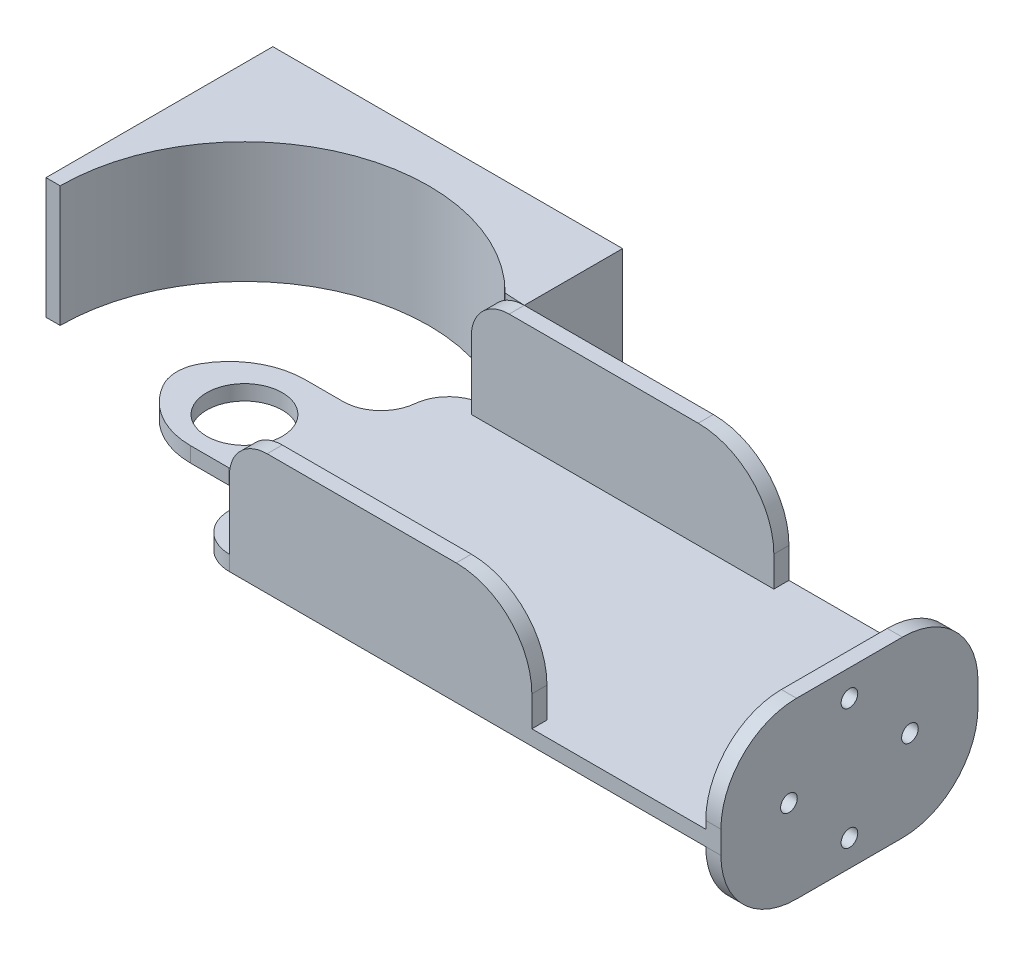
SolidWorks part; units mm, degrees
ref_plane "Plan de face" through (0, 0, 0) normal (0, 0, 1) x (1, 0, 0)
ref_plane "Plan de dessus" through (0, 0, 0) normal (0, 1, 0) x (1, 0, 0)
ref_plane "Plan de droite" through (0, 0, 0) normal (1, 0, 0) x (0, 0, -1)
sketch "Esquisse1" plane through (0, 0, 0) normal (0, 1, 0) x (1, 0, 0)
  line L0 (0, 17) -> (132.5205, 17) construction
  line L1 (0, 0) -> (70, 0)
  line L2 (0, 0) -> (0, 34)
  line L3 (0, 34) -> (70, 34)
  line L4 (70, 0) -> (70, 34)
  line L6 (0, 25) -> (-20, 25)
  line L7 (0, 25) -> (0, 9.8597)
  line L8 (0, 9.8597) -> (-20, 9.8597)
  line L9 (-20, 25) -> (-20, 9.8597)
  circle A5 centre (-10, 17) radius 5
  point P11 (109.9764, 17)
  point P21 (109.9764, 17)
  dimension "D7" = 10
  dimension "D1" = 34
  dimension "D2" = 70
  dimension "D6" = 20
extrude "Boss.-Extru.1" add sketch "Esquisse1" along normal blind 2 contours L7 L0 L4 L3 L2 | L0 L2 L1 L4 | L6 L9 L8 L2 L7 A5 region at (35, 0, -17) region at (-10, 0, -10.1105)
fillet "Congé1" radius 10 2 edges at (-20, 1, -25) (-20, 1, -9.8597)
fillet "Congé3" radius 5 1 edges at (-19.7003, 1, -17.4298)
fillet "Congé4" radius 5 2 edges at (0, 1, 0) (0, 1, -34)
fillet "Congé5" radius 5 2 edges at (0, 1, -25) (0, 1, -9.8597)
sketch "Esquisse2" plane through (0, 2, 0) normal (0, 1, 0) x (1, 0, 0)
  line L0 (70, 17) -> (-5, 17) construction
  line L1 (70, 0) -> (70, 34) construction
  line L2 (5, 0) -> (5, 2)
  line L3 (5, 34) -> (45, 34)
  line L4 (5, 34) -> (5, 32)
  line L5 (5, 32) -> (45, 32)
  line L6 (45, 34) -> (45, 32)
  line L7 (5, 2) -> (45, 2)
  line L8 (45, 0) -> (45, 2)
  line L9 (5, 0) -> (45, 0)
  circle A0 centre (-10, 17) radius 5 construction
  dimension "D1" = 40
  dimension "D2" = 2
extrude "Boss.-Extru.2" add sketch "Esquisse2" along normal blind 14
fillet "Congé6" radius 5 2 edges at (5, 16, -1) (5, 16, -33)
fillet "Congé7" radius 10 2 edges at (45, 16, -33) (45, 16, -1)
sketch "Esquisse4" plane through (0, 16, 0) normal (0, 1, 0) x (1, 0, 0)
  line L0 (-36.2488, 17) -> (-34.3741, 17)
  line L1 (10, 34) -> (7.3255, 34.1442)
  line L2 (-36.2488, 17) -> (-36.2488, 47) construction
  line L3 (10, 34) -> (10, 97.0766) construction
  line L4 (-36.2488, 47) -> (10, 47) construction
  line L5 (10, 47) -> (10, 97.0766) construction
  line L6 (-34.3741, 17) -> (-34.3741, 47) construction
  line L7 (7.3255, 34.1442) -> (7.3255, 47) construction
  line L8 (-36.2488, 17) -> (-36.2488, 47)
  line L9 (-36.2488, 47) -> (10, 47)
  line L10 (10, 47) -> (10, 34)
  arc A0 (10, 34) -> (-36.2488, 17) centre (-10, 17) ccw
  arc A1 (-34.3741, 17) -> (7.3255, 34.1442) centre (-10, 17) cw
  dimension "D1" = 30
extrude "Boss.-Extru.3" add sketch "Esquisse4" against normal up to surface (16 mm away) separate body contours A0 L10 L9 L8 | L0 A1 L1 A0 region at (-18.8726, 16, -41.138) region at (-35.6975, 16, -32) up to face at (6.7139, 0, -17.2507)
sketch "Esquisse5" plane through (70, 0, 0) normal (1, 0, 0) x (0, 0, -1)
  line L0 (34, 6) -> (34, 16) construction
  line L1 (0, 0) -> (34, 0)
  line L2 (0, 0) -> (0, 13)
  line L3 (0, 13) -> (34, 13)
  line L4 (34, 0) -> (34, 13)
  line L5 (34, 0) -> (34, 16) construction
  line L7 (34, 0) -> (0, 0)
  line L8 (34, 0) -> (34, -10)
  line L9 (34, -10) -> (0, -10)
  line L10 (0, 0) -> (0, -10)
  line M1 (0, 0) -> (34, 0)
  line M3 (34, 2) -> (0, 2)
  dimension "D1" = 13
  dimension "D2" = 10
extrude "Boss.-Extru.4" add sketch "Esquisse5" against normal blind 2 contours L4 L3 L2 M3 | L10 L9 L8 M1 region at (70, -5, -17) region at (70, 7.5, -17)
sketch "Esquisse7" plane through (70, 0, 0) normal (1, 0, 0) x (0, 0, -1)
  line L0 (17, 13) -> (17, -10) construction
  line L1 (0, 13) -> (34, 13) construction
  line L2 (34, -10) -> (0, -10) construction
  line L3 (0, 1.5) -> (34, 1.5) construction
  line L4 (0, 13) -> (0, -10) construction
  line L5 (34, 13) -> (34, -10) construction
  circle A0 centre (25, 1.5) radius 1.1
  circle A1 centre (17, -6.5) radius 1.1
  circle A2 centre (9, 1.5) radius 1.1
  circle A3 centre (17, 9.5) radius 1.1
  point P14 (17, 1.5)
  point P24 (17, 1.5)
  dimension "D1" = 2.2
  dimension "D2" = 8
  dimension "D3" = 4
extrude "Enlèv. mat.-Extru.1" cut sketch "Esquisse7" against normal blind 2
fillet "Congé8" radius 10 4 edges at (69, -10, 0) (69, -10, -34) (69, 13, -34) (69, 13, 0)
